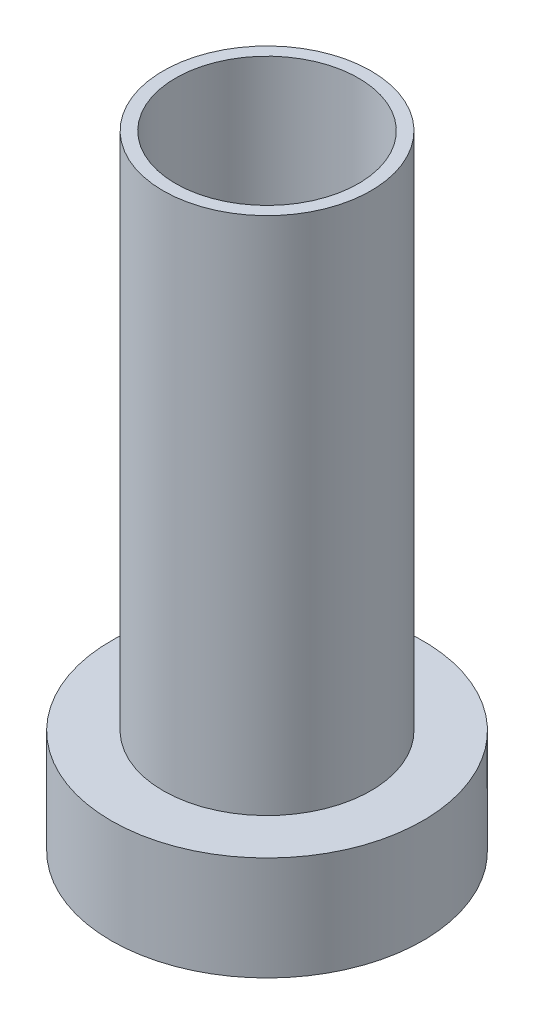
SolidWorks part; units mm, degrees
ref_plane "Front Plane" through (0, 0, 0) normal (0, 0, 1) x (1, 0, 0)
ref_plane "Top Plane" through (0, 0, 0) normal (0, 1, 0) x (1, 0, 0)
ref_plane "Right Plane" through (0, 0, 0) normal (1, 0, 0) x (0, 0, -1)
sketch "Sketch2" plane through (0, 0, 0) normal (0, 1, 0) x (1, 0, 0)
  circle A0 centre (0, 0) radius 0.75
  circle A1 centre (0, 0) radius 0.315
  circle A2 centre (0, 0) radius 0.5
  circle A3 centre (0, 0) radius 0.44
  dimension "D1" = 1.5
  dimension "D2" = 0.63
  dimension "D3" = 1
  dimension "D4" = 0.88
extrude "Boss-Extrude1" add sketch "Sketch2" along normal blind 0.5 contours A3 A1 | A2 A3 | A0 A2 region at (-0.7288, 0, 0) region at (-0.4859, 0, 0) region at (-0.4276, 0, 0)
extrude "Boss-Extrude2" add sketch "Sketch2<3>" along normal blind 2.5 from surface contours A2 A3 region at (-0.4859, 0, 0) starting at face at (0, 0.5, 0.315)
sketch "Sketch2<3>" plane through (0, 0, 0) normal (0, 1, 0) x (1, 0, 0) same geometry as "Sketch2"
